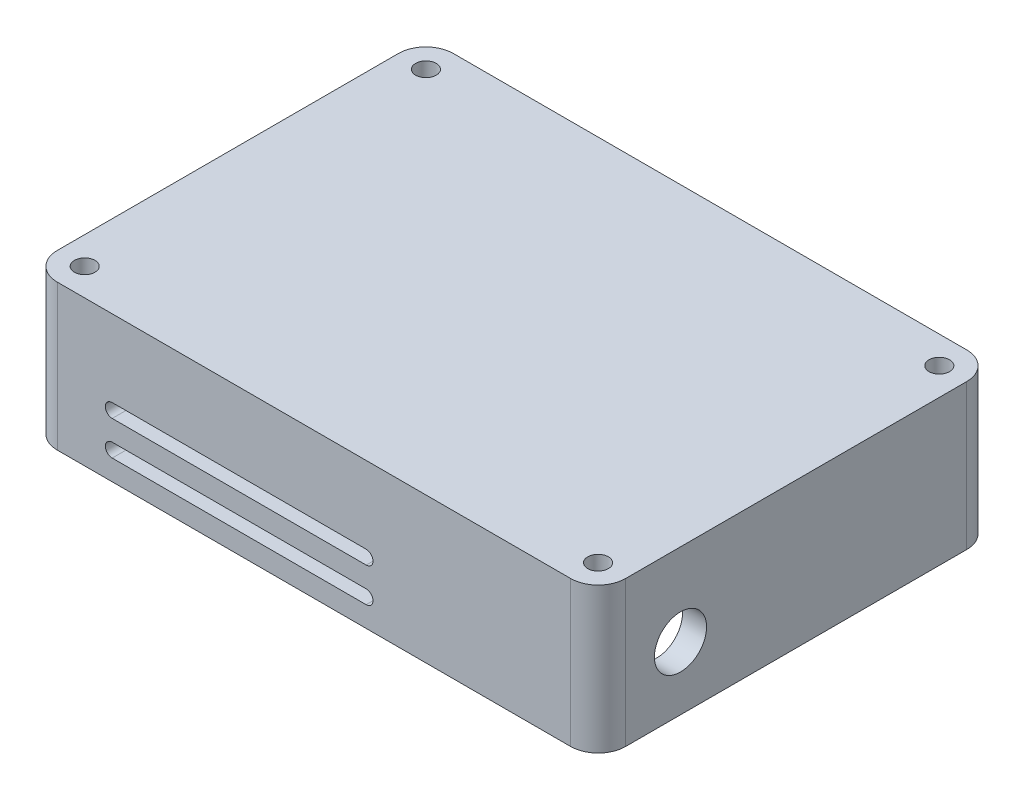
SolidWorks part; units mm, degrees
material "ABS"
ref_plane "Front Plane" through (0, 0, 0) normal (0, 0, 1) x (1, 0, 0)
ref_plane "Top Plane" through (0, 0, 0) normal (0, 1, 0) x (1, 0, 0)
ref_plane "Right Plane" through (0, 0, 0) normal (1, 0, 0) x (0, 0, -1)
sketch "Sketch1" plane through (0, 0, 0) normal (0, 1, 0) x (1, 0, 0)
  line L1 (-109.9297, 31.1354) -> (-27.1297, 31.1354)
  line L2 (-109.9297, 31.1354) -> (-109.9297, -26.5646)
  line L3 (-109.9297, -26.5646) -> (-27.1297, -26.5646)
  line L4 (-27.1297, 31.1354) -> (-27.1297, -26.5646)
  line L5 (-109.9297, 31.1354) -> (-27.1297, -26.5646) construction
  line L6 (-109.9297, -26.5646) -> (-27.1297, 31.1354) construction
  point P0 (-68.5297, 2.2854)
extrude "Boss-Extrude1" add sketch "Sketch1" along normal blind 21.2
sketch "Sketch2" plane through (0, 0, 0) normal (0, -1, 0) x (1, 0, 0)
  line L0 (-27.1297, 26.5646) -> (-27.1297, -31.1354) construction
  line L1 (-109.9297, -31.1354) -> (-109.9297, 26.5646) construction
  circle A0 centre (-105.9297, 22.5741) radius 1.5
  circle A1 centre (-31.1297, 22.5741) radius 1.5
  circle A2 centre (-105.9297, -27.1448) radius 1.5
  circle A3 centre (-31.1297, -27.1448) radius 1.5
  dimension "D1" = 4
  dimension "D2" = 4
  dimension "D3" = 4
  dimension "D4" = 4
extrude "Cut-Extrude1" cut sketch "Sketch2" against normal blind 22
sketch "Sketch3" plane through (0, 0, 0) normal (0, -1, 0) x (1, 0, 0)
  line L1 (-101.9693, 23.0646) -> (-35.09, 23.0646)
  line L2 (-106.4297, 18.6072) -> (-106.4297, -23.175)
  line L3 (-101.9693, -27.6354) -> (-35.09, -27.6354)
  line L4 (-30.6297, 18.6043) -> (-30.6297, -23.175)
  line L5 (-103.3343, 24.0646) -> (-33.7237, 24.0646)
  line L6 (-29.6297, 19.9706) -> (-29.6297, -24.5413)
  line L10 (-103.3356, -28.6354) -> (-33.7237, -28.6354)
  line L11 (-107.4297, 19.9733) -> (-107.4297, -24.5413)
  line L13 (-106.4297, -23.175) -> (-106.4297, 18.6043) construction
  arc A0 (-106.4297, 18.6072) -> (-101.9693, 23.0646) centre (-105.9395, 22.577) ccw
  arc A1 (-35.09, 23.0646) -> (-30.6297, 18.6043) centre (-31.1202, 22.5741) ccw
  arc A2 (-30.6297, -23.175) -> (-35.09, -27.6354) centre (-31.1202, -27.1448) ccw
  arc A3 (-101.9693, -27.6354) -> (-106.4297, -23.175) centre (-105.9391, -27.1448) ccw
  arc A4 (-33.7237, 24.0646) -> (-29.6297, 19.9706) centre (-31.1202, 22.5741) ccw
  arc A5 (-29.6297, -24.5413) -> (-33.7237, -28.6354) centre (-31.1202, -27.1448) ccw
  arc A6 (-103.3356, -28.6354) -> (-107.4297, -24.5413) centre (-105.9391, -27.1448) ccw
  arc A7 (-107.4297, 19.9733) -> (-103.3343, 24.0646) centre (-105.9395, 22.577) ccw
  arc A8 (-30.6297, -23.175) -> (-35.09, -27.6354) centre (-31.1202, -27.1448) ccw construction
  point P0 (-67.3297, -2.2854)
  dimension "D5" = 1
extrude "Cut-Extrude2" cut sketch "Sketch3" against normal blind 20 contours A0 L1 A1 L4 A2 L3 A3 L2
fillet "Fillet3" radius 4 4 edges at (-27.1297, 10.6, 26.5646) (-109.9297, 10.6, 26.5646) (-109.9297, 10.6, -31.1354) (-27.1297, 10.6, -31.1354)
extrude "Boss-Extrude3" add sketch "Sketch3<8>" along normal blind 1
sketch "Sketch3<8>" plane through (0, 0, 0) normal (0, -1, 0) x (1, 0, 0) same geometry as "Sketch3"
sketch "Sketch7" plane through (0, 0, -31.1354) normal (0, 0, -1) x (-1, 0, 0)
  line L0 (97.9297, 3) -> (60.9297, 3)
  line L1 (97.9297, 5) -> (60.9297, 5)
  line L2 (97.9297, 3) -> (97.9297, 5) construction
  line L3 (60.9297, 3) -> (60.9297, 5) construction
  line L4 (109.9297, 21.2) -> (109.9297, 0) construction
  line L5 (31.1297, 0) -> (105.9297, 0) construction
  line L6 (97.9297, 8) -> (60.9297, 8)
  line L7 (97.9297, 10) -> (60.9297, 10)
  line L8 (97.9297, 8) -> (97.9297, 10) construction
  line L9 (60.9297, 8) -> (60.9297, 10) construction
  arc A0 (97.9297, 3) -> (97.9297, 5) centre (97.9297, 4) ccw
  arc A1 (60.9297, 5) -> (60.9297, 3) centre (60.9297, 4) ccw
  arc A2 (97.9297, 8) -> (97.9297, 10) centre (97.9297, 9) ccw
  arc A3 (60.9297, 10) -> (60.9297, 8) centre (60.9297, 9) ccw
  dimension "D2" = 37
  dimension "D3" = 12
  dimension "D1" = 2
  dimension "D4" = 3
  dimension "D5" = 2
extrude "Cut-Extrude6" cut sketch "Sketch7" against normal through all contours L7 A3 L6 A2 | L1 A1 L0 A0 region at (-79.4297, 4, -31.1354) region at (-79.4297, 9, -31.1354)
sketch "Sketch8" plane through (-109.9297, 0, 0) normal (-1, 0, 0) x (0, 0, 1)
  line L0 (26.5646, 21.2) -> (26.5646, 0) construction
  line L1 (-27.1354, 21.2) -> (22.5646, 21.2) construction
  circle A0 centre (14.5646, 9.2) radius 3.8
  dimension "D1" = 12
  dimension "D2" = 12
extrude "Cut-Extrude7" cut sketch "Sketch8" against normal through all
